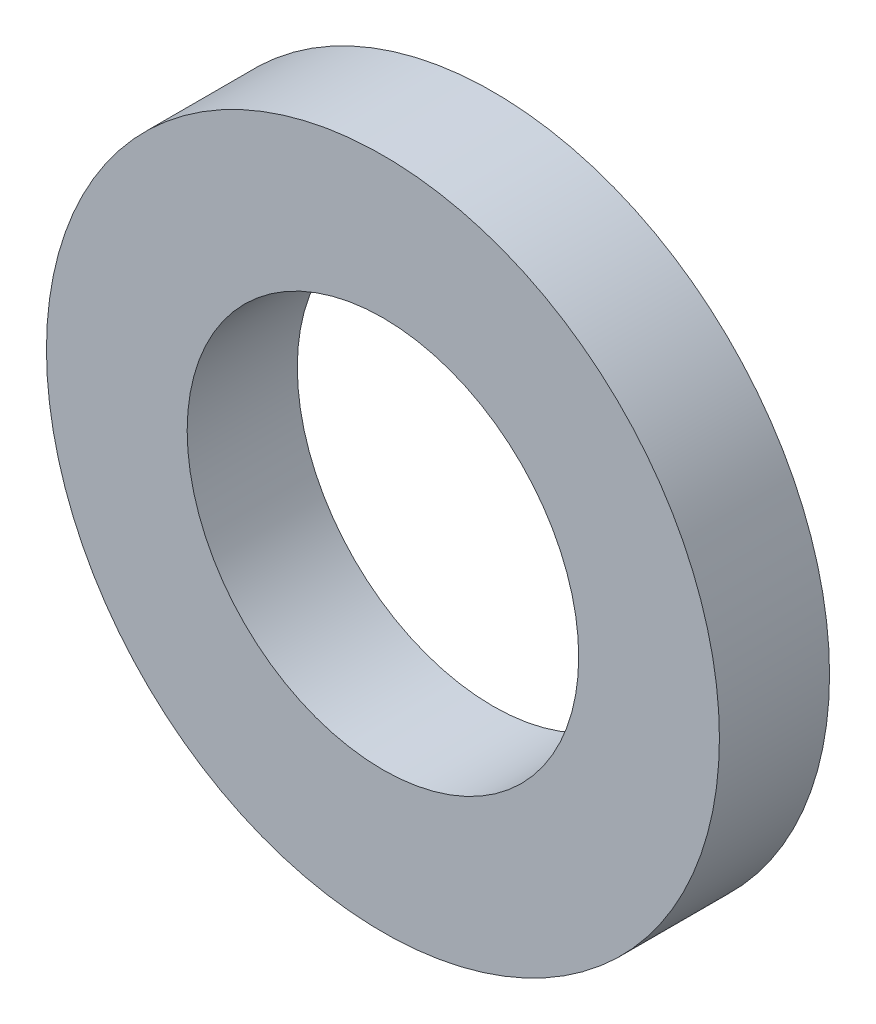
SolidWorks part; units mm, degrees
ref_plane "Front Plane" through (0, 0, 0) normal (0, 0, 1) x (1, 0, 0)
ref_plane "Top Plane" through (0, 0, 0) normal (0, 1, 0) x (1, 0, 0)
ref_plane "Right Plane" through (0, 0, 0) normal (1, 0, 0) x (0, 0, -1)
sketch "Sketch1" plane through (0, 0, 0) normal (0, 0, 1) x (1, 0, 0)
  circle A0 centre (0, 0) radius 5.5
  circle A1 centre (0, 0) radius 3.2
  dimension "OD" = 11
  dimension "ID1" = 6.4
extrude "Boss-Extrude1" add sketch "Sketch1" along normal blind 1.8
ref_axis "Center Axis 1" through (0, 0, 1.8) along (0, 0, -1)
ref_plane "Contact Plane 1" through (0, 0, 1.8) normal (0, 0, 1) x (1, 0, 0)
ref_plane "Contact Plane 2" through (0, 0, 0) normal (0, 0, -1) x (-1, 0, 0)
